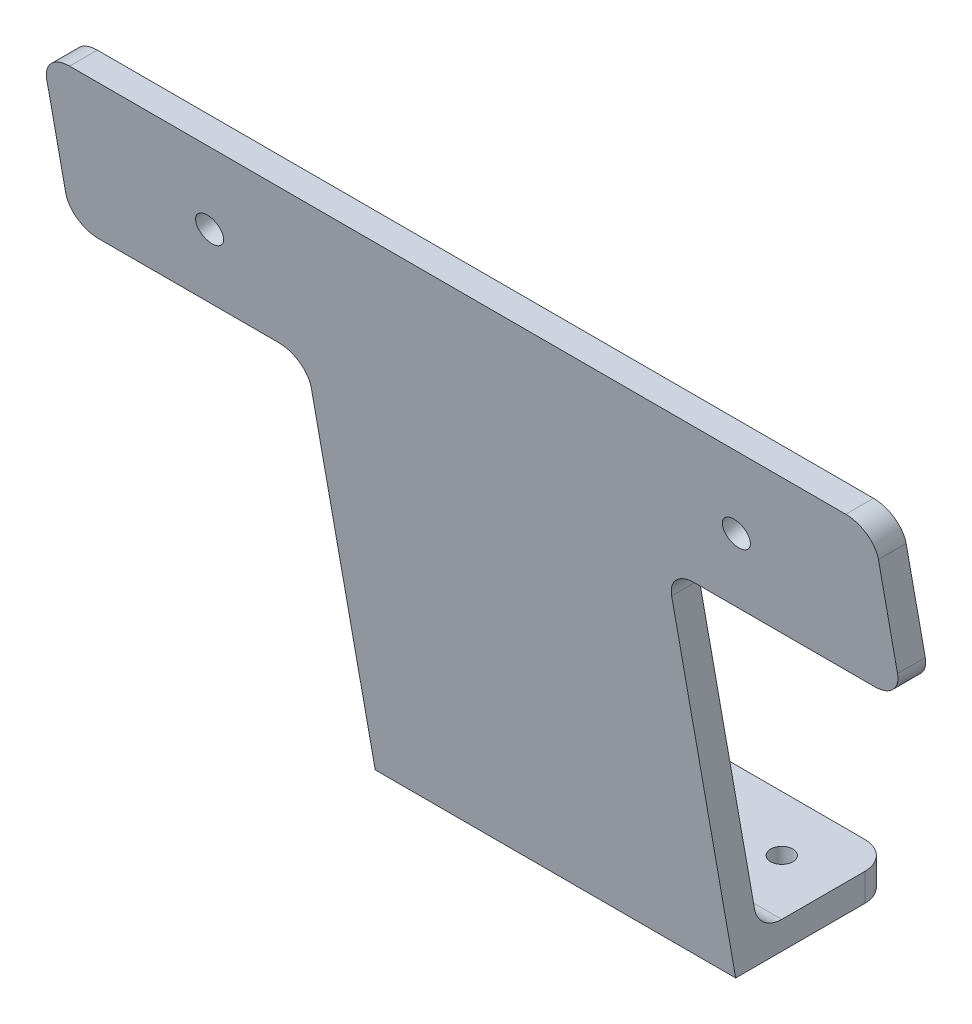
SolidWorks part; units mm, degrees
ref_plane "Front Plane" through (0, 0, 0) normal (0, 0, 1) x (1, 0, 0)
ref_plane "Top Plane" through (0, 0, 0) normal (0, 1, 0) x (1, 0, 0)
ref_plane "Right Plane" through (0, 0, 0) normal (1, 0, 0) x (0, 0, -1)
sketch "Sketch1" plane through (0, 0, 0) normal (1, 0, 0) x (0, 0, -1)
  line L0 (-17.6327, 100) -> (0, 0)
  line L1 (0, 0) -> (28.3, 0)
  line L2 (28.3, 0) -> (28.3, 5)
  line L3 (28.3, 5) -> (4.1184, 5)
  line L4 (4.1184, 5) -> (-12.6327, 100)
  line L5 (-12.6327, 100) -> (-17.6327, 100)
  dimension "D1" = 5
  dimension "D2" = 28.3
  dimension "D3" = 100
  dimension "D4" = 100
extrude "Boss-Extrude1" add sketch "Sketch1" along normal blind 65
sketch "Sketch2" plane through (0, 0, 0) normal (0, -0.1736, 0.9848) x (1, 0, 0)
  line L1 (-42.5, 101.5427) -> (107.5, 101.5427)
  line L2 (-42.5, 101.5427) -> (-42.5, 71.5427)
  line L3 (-42.5, 71.5427) -> (107.5, 71.5427)
  line L4 (107.5, 101.5427) -> (107.5, 71.5427)
  line L5 (65, 101.5427) -> (0, 101.5427) construction
  point P6 (32.5, 101.5427)
  point P7 (32.5, 101.5427)
  dimension "D1" = 150
  dimension "D2" = 30
extrude "Boss-Extrude2" add sketch "Sketch2" along direction (0, 0, 1) on the side against the normal up to surface (4.924 mm away) up to face at (32.5, 52.5, 4.2572)
fillet "Fillet1" radius 5 9 edges at (32.5, 5, -4.1184) (107.5, 70.4558, 9.9233) (107.5, 100, 15.1327) (-42.5, 100, 15.1327) (-42.5, 70.4558, 9.9233) (0, 2.5, -28.3) (65, 2.5, -28.3) (0, 70.4558, 9.9233) (65, 70.4558, 9.9233)
sketch "Sketch3" plane through (0, 5, 0) normal (0, 1, 0) x (1, 0, 0)
  line L0 (65, 23.3) -> (65, 8.3139) construction
  line L1 (0, 23.3) -> (0, 8.3139) construction
  line L3 (0, 8.3139) -> (65, 8.3139) construction
  circle A0 centre (10, 18.3139) radius 2
  circle A1 centre (55, 18.3139) radius 2
  dimension "D1" = 4
  dimension "D2" = 10
  dimension "D3" = 10
  dimension "D4" = 10
extrude "Cut-Extrude1" cut sketch "Sketch3" against normal up to next
ref_plane "Plane1" through (32.5, 0, 0) normal (-1, 0, 0) x (0, 0, 1)
sketch "Sketch5" plane through (0, 0.8551, -4.8492) normal (0, 0.1736, -0.9848) x (-1, 0, 0)
  line L0 (-80, 85.6744) -> (15, 85.6744) construction
  line L3 (-102.5, 100.6744) -> (37.5, 100.6744) construction
  line L4 (-107.5, 95.5973) -> (-107.5, 75.7516) construction
  circle A0 centre (-80, 85.6744) radius 2.5
  circle A1 centre (15, 85.6744) radius 2.5
  point P3 (-32.5, 100.6744)
  point P8 (-32.5, 85.6744)
  point P11 (-107.5, 85.6744)
  dimension "D2" = 5
  dimension "D3" = 5
  dimension "D1" = 95
extrude "Cut-Extrude2" cut sketch "Sketch5" against normal through all
sketch "Sketch9" plane through (32.5, 0, 0) normal (-1, 0, 0) x (0, 0, 1)
  line L1 (7.4233, 70.4558) -> (6.5416, 65.4558) construction
  line L3 (-23.3, 5) -> (-28.3, 5) construction
  line L4 (-25.1003, 5) -> (-8.3139, 5)
  line L5 (7.1307, 68.7968) -> (-3.3898, 9.1318)
  line L6 (-25.1003, 5) -> (7.1307, 68.7968)
  arc A0 (-8.3139, 5) -> (-3.3898, 9.1318) centre (-8.3139, 10) ccw
extrude "Boss-Extrude3" add sketch "Sketch9" along normal blind 4 and the other way blind 4 contours L4 A0 L5 L6
